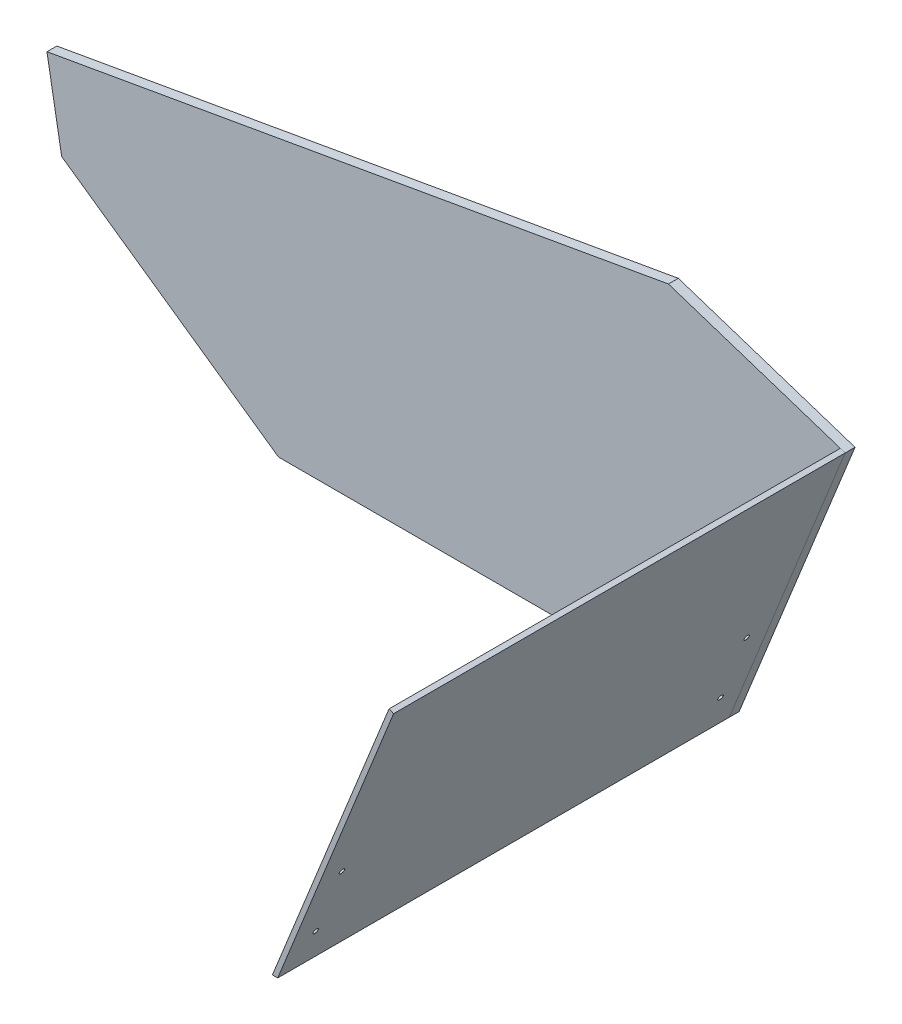
SolidWorks part; units mm, degrees
material "Melamine"
ref_plane "Front Plane" through (0, 0, 0) normal (0, 0, 1) x (1, 0, 0)
ref_plane "Top Plane" through (0, 0, 0) normal (0, 1, 0) x (1, 0, 0)
ref_plane "Right Plane" through (0, 0, 0) normal (1, 0, 0) x (0, 0, -1)
ref_axis "Axis1" through (0, 0, -14.8175) along (0, 0, 1)
sketch "Sketch1" plane through (0, 0, 0) normal (0, 0, 1) x (1, 0, 0)
  line L0 (-140, 0) -> (140, 0) construction
  line L1 (-140, 0) -> (-303.8304, 114.7153) construction
  line L4 (-151.0709, 0) -> (-307.4726, 109.5137) construction
  line L5 (-307.4726, 109.5137) -> (-303.8304, 114.7153) construction
  line L11 (140, 0) -> (143.4243, 0)
  line L12 (140, 0) -> (214.9213, 185.4368) construction
  line L14 (143.4243, 0) -> (217.8651, 184.2474)
  line L15 (217.8651, 184.2474) -> (214.9213, 185.4368)
  line L16 (214.9213, 185.4368) -> (140, 0)
  line L17 (-140, 0) -> (-151.0709, 0) construction
  point P4 (0, 0)
  dimension "D1" = 35
  dimension "D2" = 280
  dimension "D4" = 200
  dimension "D6" = 6.35
  dimension "D7" = 68
  dimension "D8" = 200
  dimension "D9" = 3.175
extrude "Boss-Extrude1" add sketch "Sketch1" along normal blind 290
sketch "Sketch2" plane through (0, 0, 0) normal (0, 0, 1) x (1, 0, 0)
  line L1 (-294.7779, 151.108) -> (104.3699, 221.4886)
  line L3 (143.4243, 0) -> (-146.0709, 0)
  line L4 (-146.0709, 0) -> (-285.3267, 97.508) construction
  line L5 (143.4243, 0) -> (217.8651, 184.2474)
  line L7 (-285.3267, 97.508) -> (-294.7779, 151.108)
  line L8 (-285.3267, 97.508) -> (-281.6845, 102.7096) construction
  line L9 (217.8651, 184.2474) -> (104.3699, 221.4886)
  line L10 (143.4243, 0) -> (104.3699, 221.4886) construction
  line L11 (-285.3267, 97.508) -> (-146.0709, 0)
  line L13 (-146.0709, 0) -> (-135, 0) construction
  line L14 (-285.3267, 97.508) -> (-146.0709, 0) construction
  line L15 (-281.6845, 102.7096) -> (-135, 0) construction
  dimension "D1" = 10
  dimension "D2" = 200
  dimension "D3" = 6.35
  dimension "D4" = 35
  dimension "D5" = 170
  dimension "D6" = 275
extrude "Boss-Extrude2" add sketch "Sketch2" against normal blind 6.35 separate body
ref_plane "HOLDING PLANE" through (0, 0, 0) normal (0.9848, 0.1736, 0) x (0, 0, 1)
ref_point "Walls Center"
hole_wizard "M3 Clearance Hole1" positions "Sketch3" profile "Sketch4" hole size "M3" standard "ANSI Metric" end condition through all
sketch "Sketch3" plane through (123.2976, -49.8155, 0) normal (0.9272, -0.3746, 0) x (0, 0, -1)
  line L0 (0, 53.7277) -> (0, 252.4449) construction
  line L1 (-290, 53.7277) -> (0, 53.7277) construction
  point P0 (-275, 123.7277)
  point P3 (-275, 78.7277)
  point P6 (-15, 123.7277)
  point P9 (-15, 78.7277)
  dimension "D1" = 15
  dimension "D2" = 25
sketch "Sketch4" plane through (169.6468, 64.9029, 275) normal (0, 0, 1) x (0.3746, 0.9272, 0)
  line L0 (0, 0) -> (0, 489.2651)
  line L1 (0, 489.2651) -> (1.7, 489.2651)
  line L2 (1.7, 489.2651) -> (1.7, 0.025)
  line L3 (1.7, 0.025) -> (1.725, 0)
  line L5 (1.725, 0) -> (0, 0)
  line L6 (-1.7, 0.025) -> (-1.725, 0) construction
  line L11 (0, -6.35) -> (0, 107.95) construction
  dimension "Thru Hole Dia." = 3.4
  dimension "Thru Hole Depth" = 489.2651
  dimension "Near C'Sink Dia." = 3.45
  dimension "Near C'Sink Angle" = 90
